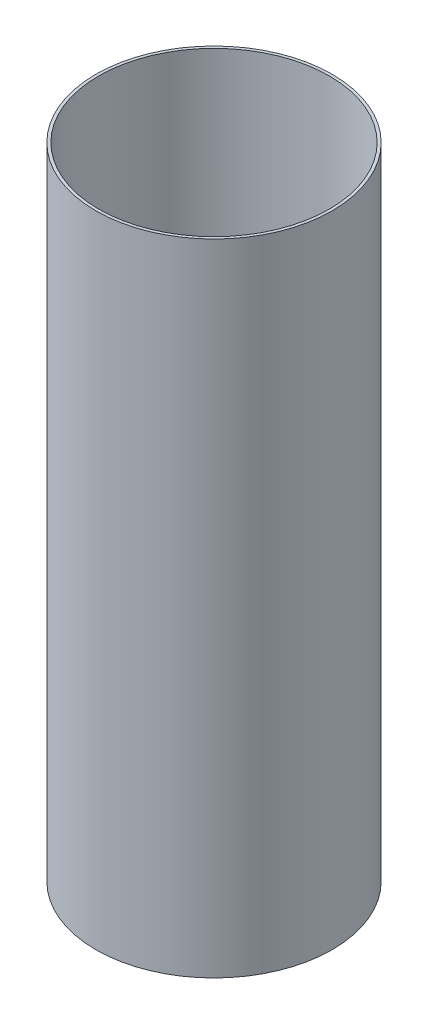
SolidWorks part; units mm, degrees
ref_plane "Спереди" through (0, 0, 0) normal (0, 0, 1) x (1, 0, 0)
ref_plane "Сверху" through (0, 0, 0) normal (0, 1, 0) x (1, 0, 0)
ref_plane "Справа" through (0, 0, 0) normal (1, 0, 0) x (0, 0, -1)
sketch "lower_side" plane through (0, 0, 0) normal (0, 1, 0) x (1, 0, 0)
  circle A0 centre (0, 0) radius 33.25
  dimension "D1" = 66.5
ref_plane "Плоскость1" through (0, 180, 0) normal (0, 1, 0) x (1, 0, 0)
extrude "Main_body" add sketch "lower_side" along normal blind 180 separate body thin thin type one direction reverse wall 0.8
extrude "Bottom" add sketch "Эскиз1<5>" along normal blind 1.2
sketch "Эскиз1<5>" plane through (0, 0, 0) normal (0, 1, 0) x (1, 0, 0) same geometry as "lower_side"
sketch "bottom_cut_draft" plane through (0, 0, 0) normal (0, -1, 0) x (1, 0, 0)
  line L1 (-6, 31.5) -> (6, 31.5)
  line L2 (-6, 31.5) -> (-6, -31.5)
  line L3 (-6, -31.5) -> (6, -31.5)
  line L4 (6, 31.5) -> (6, -31.5)
  line L5 (-10.8743, 8) -> (-32.2732, 8)
  line L6 (-12.0934, 6) -> (-32.8445, 6)
  line L8 (11.9724, -6.2378) -> (32.7235, -6.2378)
  line L9 (10.8743, -8) -> (32.2732, -8)
  circle A0 centre (0, 0) radius 13.5
  circle A2 centre (0, 0) radius 33.25 construction
  arc A3 (-32.2732, 8) -> (-32.7042, 6) centre (0, 0) ccw
  arc A4 (32.2732, -8) -> (32.6596, -6.2378) centre (0, 0) ccw
  point P7 (0, 31.5)
  point P8 (-6, 0)
  point P10 (0, -31.5)
  point P12 (32.7235, -6.2378)
  dimension "D1" = 27
  dimension "D2" = 12
  dimension "D3" = 63
  dimension "D4" = 6
  dimension "D5" = 2
extrude "Bottom_cut" cut sketch "bottom_cut_draft" against normal blind 1.2 contours L4 A0 L2 | L4 A0 | L2 A0 | A0 L4 L1 L2 | A0 L2 L3 L4 region at (0, 0, 22.266) region at (0, 0, 0) region at (-9.0853, 0, 0) region at (9.0853, 0, 0) region at (0, 0, -22.266)
sketch "slope_draft" plane through (0, 0, 0) normal (0, 0, 1) x (1, 0, 0)
  line L1 (0, 4.6996) -> (0, -2.2518) construction
  line L2 (6, 1.2) -> (6, 0) construction
  line L3 (6, 1.2) -> (6, 0)
  line L4 (13.5, 1.2) -> (6, 1.2) construction
  line L8 (13.5, 1.2) -> (6, 1.2)
  line L9 (-6, 0.4) -> (-13.5, 1.2)
  line L10 (6, 0) -> (13.5, 0)
  line L11 (-6, 0) -> (-13.5, 0)
  line L16 (6, 0.4) -> (13.5, 1.2)
  line L17 (-13.5, 1.2) -> (-6, 1.2)
  line L18 (-6, 1.2) -> (-6, 0)
  dimension "D1" = 0.4
extrude "Slope_1" cut sketch "slope_draft" along normal up to surface (29.5085 mm away) contours L3 L16 L8 region at (8.5, 0.9333, 0) up to face at (0, 1.2, 32.45)
extrude "Slope_2" cut sketch "Эскиз6<3>" against normal up to surface (31.8905 mm away) contours L18 L17 L9 region at (-8.5, 0.9333, 0) up to face at (2, 0.9359, 10.6302)
sketch "Эскиз6<3>" plane through (0, 0, 0) normal (0, 0, 1) x (1, 0, 0) same geometry as "slope_draft"
extrude "Stopper" add sketch "Эскиз5<3>" against normal blind 3 draft 1 contours A0 L9 L8 | A0 L5 L6 region at (-22.0089, 0, 7.0062) region at (21.9627, 0, -7.1239)
sketch "Эскиз5<3>" plane through (0, 0, 0) normal (0, -1, 0) x (1, 0, 0) same geometry as "bottom_cut_draft"
